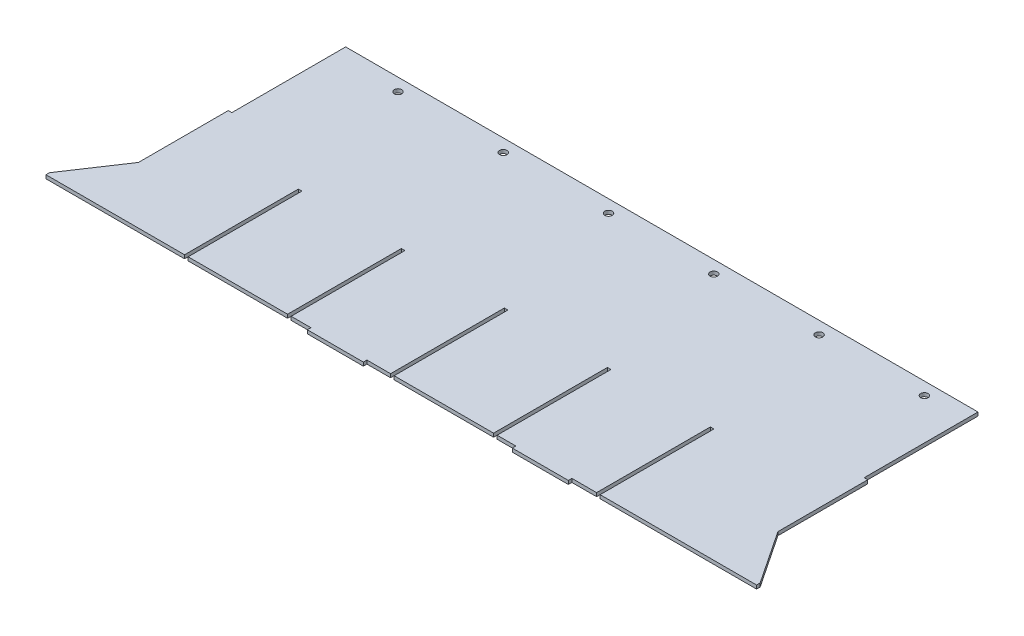
SolidWorks part; units mm, degrees
material "Custom Plastic"
ref_plane "X-Y Datum" through (0, 0, 0) normal (0, 0, 1) x (1, 0, 0)
ref_plane "X-Z Datum" through (0, 0, 0) normal (0, 1, 0) x (1, 0, 0)
ref_plane "Y-Z Datum" through (0, 0, 0) normal (1, 0, 0) x (0, 0, -1)
sketch "Sketch1" plane through (0, 0, 0) normal (0, 0, 1) x (1, 0, 0)
  line L1 (-285.4305, -1.5875) -> (285.4305, -1.5875)
  line L2 (-285.4305, -1.5875) -> (-285.4305, 1.5875)
  line L3 (-285.4305, 1.5875) -> (285.4305, 1.5875)
  line L4 (285.4305, -1.5875) -> (285.4305, 1.5875)
  line L5 (-285.4305, -1.5875) -> (285.4305, 1.5875) construction
  line L6 (-285.4305, 1.5875) -> (285.4305, -1.5875) construction
  point P0 (0, 0)
  dimension "D1" = 570.861
  dimension "D2" = 3.175
extrude "Boss-Extrude1" add sketch "Sketch1" along normal blind 232.6
sketch "Sketch2" plane through (0, 1.5875, 0) normal (0, 1, 0) x (1, 0, 0)
  line L0 (-176.5505, -181.8) -> (-285.4305, -181.8) construction
  line L1 (-285.4305, -232.6) -> (-285.4305, 0) construction
  line L3 (285.4305, -232.6) -> (-285.4305, -232.6) construction
  line L4 (-178.0615, -232.6) -> (-174.8865, -232.6)
  line L6 (-178.0615, -118.3) -> (-174.8865, -118.3)
  line L8 (-178.0615, -232.6) -> (-174.8865, -232.6)
  line L9 (-178.0615, -232.6) -> (-178.0615, -118.3)
  line L10 (-178.0615, -118.3) -> (-174.8865, -118.3)
  line L11 (-174.8865, -232.6) -> (-174.8865, -118.3)
  line L17 (-178.0615, -118.3) -> (-174.8865, -118.3)
  line L38 (-285.4305, 0) -> (-282.2555, 0)
  line L39 (-285.4305, 0) -> (-285.4305, -101.6)
  line L40 (-285.4305, -101.6) -> (-282.2555, -101.6)
  line L41 (-282.2555, 0) -> (-282.2555, -101.6)
  line L42 (285.4305, 0) -> (282.2555, 0)
  line L43 (285.4305, 0) -> (285.4305, -101.6)
  line L44 (285.4305, -101.6) -> (282.2555, -101.6)
  line L45 (282.2555, 0) -> (282.2555, -101.6)
  line M3 (285.4305, 0) -> (-285.4305, 0)
  line M4 (-285.4305, 0) -> (-285.4305, -232.6)
  line M6 (285.4305, -232.6) -> (285.4305, 0)
  dimension "D2" = 50.8
  dimension "D3" = 3.175
  dimension "D6" = 3.175
  dimension "D7" = 101.6
  dimension "D4" = 114.3
  dimension "D8" = 3.175
  dimension "D9" = 101.6
sketch "Sketch6" plane through (0, 0, 232.6) normal (0, 0, 1) x (1, 0, 0)
  line L0 (285.4305, 1.5875) -> (-285.4305, 1.5875) construction
  line L1 (-285.4305, 1.5875) -> (-285.4305, -1.5875) construction
  line L14 (152.263, -1.5875) -> (152.263, 1.5875)
  line L15 (102.263, 1.5875) -> (152.263, 1.5875)
  line L16 (102.263, -1.5875) -> (152.263, 1.5875) construction
  line L17 (102.263, 1.5875) -> (152.263, -1.5875) construction
  line L18 (102.263, -1.5875) -> (152.263, -1.5875)
  line L19 (102.263, -1.5875) -> (102.263, 1.5875)
  line L20 (-30.6951, -1.5875) -> (-30.6951, 1.5875)
  line L21 (-80.6951, 1.5875) -> (-30.6951, 1.5875)
  line L22 (-80.6951, -1.5875) -> (-30.6951, 1.5875) construction
  line L23 (-80.6951, 1.5875) -> (-30.6951, -1.5875) construction
  line L24 (-80.6951, -1.5875) -> (-30.6951, -1.5875)
  line L25 (-80.6951, -1.5875) -> (-80.6951, 1.5875)
  point P4 (-55.6951, 0)
  point P5 (127.263, 0)
  point P7 (0, 0)
  dimension "D1" = 3.175
  dimension "D2" = 50
  dimension "D3" = 3.175
  dimension "D4" = 229.7354
  dimension "D5" = 182.9581
sketch "Sketch7" plane through (0, -1.5875, 0) normal (0, -1, 0) x (-1, 0, 0)
  line L1 (-285.4305, -232.6) -> (-285.4305, 0) construction
  circle A2 centre (-245.6805, -11.2916) radius 3.302
  dimension "D1" = 39.75
  dimension "D2" = 6.604
extrude "Cut-Extrude4" cut sketch "Sketch7" against normal through all contours A2 region at (245.6805, -1.5875, 11.2916)
extrude "Boss-Extrude2" add sketch "Sketch6" along normal blind 3.175
pattern_linear "LPattern1" count 6 spacing 93.98 along (-1, 0, 0) of "Cut-Extrude4"
extrude "Cut-Extrude5" cut sketch "Sketch2" against normal through all contours L41 L40 M3 M4 | L45 L44 M3 M6 region at (283.843, 1.5875, 50.8) region at (-283.843, 1.5875, 50.8)
sketch "Sketch12" plane through (0, 1.5875, 0) normal (0, 1, 0) x (1, 0, 0)
  line L0 (-285.4305, -232.6) -> (-285.4305, -101.6) construction
  line L1 (-285.4305, -232.6) -> (-285.4305, -181.8)
  line L2 (285.4305, -232.6) -> (285.4305, -101.6) construction
  line L3 (285.4305, -232.6) -> (285.4305, -101.6)
  line L4 (-285.4305, -232.6) -> (-317.1805, -232.6)
  line L6 (-317.1805, -232.6) -> (-317.1805, -229.425)
  line L7 (-317.1805, -229.425) -> (-285.4305, -181.8)
  line M9 (-285.4305, -101.6) -> (-285.4305, -232.6)
  dimension "D1" = 31.75
  dimension "D2" = 50.8
  dimension "D3" = 3.175
extrude "Boss-Extrude3" add sketch "Sketch12" against normal blind 3.175 contours L4 M9 region at (-296.6364, 1.5875, 215.6044)
mirror "Mirror1" about plane through (0, 0, 0) normal (1, 0, 0) of "Boss-Extrude3"
sketch "Sketch13" plane through (0, -1.5875, 0) normal (0, -1, 0) x (1, 0, 0)
  line L0 (-193.4755, 232.6) -> (-193.4755, 131)
  line L1 (-317.1805, 232.6) -> (-80.6951, 232.6) construction
  line L2 (-282.2555, 0) -> (-282.2555, 101.6) construction
  line L3 (-193.4755, 232.6) -> (-190.3005, 232.6)
  line L5 (-193.4755, 232.6) -> (-193.4755, 131)
  line L6 (-193.4755, 131) -> (-190.3005, 131)
  line L7 (-190.3005, 232.6) -> (-190.3005, 131)
  line M23 (-80.6951, 232.6) -> (-317.1805, 232.6)
  dimension "D1" = 88.78
  dimension "D2" = 101.6
  dimension "D3" = 3.175
extrude "Cut-Extrude6" cut sketch "Sketch13" against normal through all contours L7 L0 L6 M23 region at (-191.888, -1.5875, 181.8)
pattern_linear "LPattern2" count 5 spacing 91.955 along (1, 0, 0) of "Cut-Extrude6"
